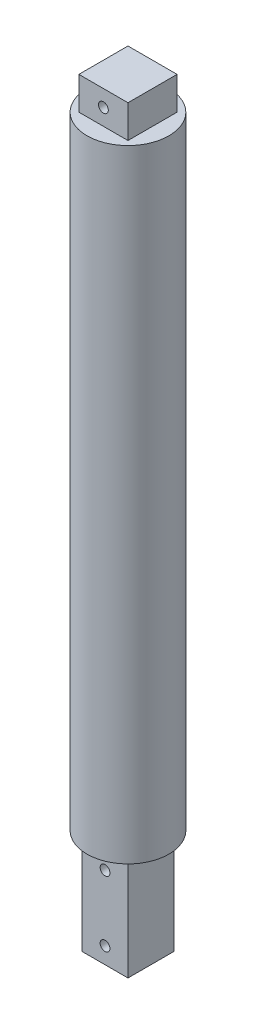
SolidWorks part; units mm, degrees
material "1060 Alloy"
ref_plane "Front Plane" through (0, 0, 0) normal (0, 0, 1) x (1, 0, 0)
ref_plane "Top Plane" through (0, 0, 0) normal (0, 1, 0) x (1, 0, 0)
ref_plane "Right Plane" through (0, 0, 0) normal (1, 0, 0) x (0, 0, -1)
sketch "Sketch1" plane through (0, 0, 0) normal (0, 0, 1) x (1, 0, 0)
  line L0 (0, 0) -> (0, -14105.0389) construction
  line L1 (-7, 32) -> (7, 32)
  line L2 (-7, 32) -> (-7, 0)
  line L3 (-7, 0) -> (7, 0)
  line L4 (7, 32) -> (7, 0)
  circle A0 centre (0, 5) radius 1.5
  circle A1 centre (0, 25) radius 1.5
  point P5 (0, 0)
  dimension "D4" = 3
  dimension "D5" = 3
  dimension "D1" = 14
  dimension "D2" = 32
  dimension "D3" = 20
  dimension "D6" = 5
extrude "Boss-Extrude1" add sketch "Sketch1" along normal mid plane 14
sketch "Sketch3" plane through (0, 32, 0) normal (0, 1, 0) x (1, 0, 0)
  circle A0 centre (0, 0) radius 12.5
  dimension "D1" = 25
extrude "Boss-Extrude2" add sketch "Sketch3" along normal blind 200
sketch "Sketch4" plane through (0, 232, 0) normal (0, 1, 0) x (1, 0, 0)
  line L1 (-7.5, 7.5) -> (7.5, 7.5)
  line L2 (-7.5, 7.5) -> (-7.5, -7.5)
  line L3 (-7.5, -7.5) -> (7.5, -7.5)
  line L4 (7.5, 7.5) -> (7.5, -7.5)
  line L5 (-7.5, 7.5) -> (7.5, -7.5) construction
  line L6 (-7.5, -7.5) -> (7.5, 7.5) construction
  point P0 (0, 0)
  dimension "D1" = 15
  dimension "D2" = 15
extrude "Cut-Extrude1" cut sketch "Sketch4" against normal blind 10 flip side to cut
sketch "Sketch5" plane through (0, 0, 7.5) normal (0, 0, 1) x (1, 0, 0)
  line L0 (-7.5, 227) -> (7.5, 227) construction
  line L1 (-7.5, 222) -> (-7.5, 232) construction
  line L2 (7.5, 222) -> (7.5, 232) construction
  line L3 (0, 232) -> (0, 222) construction
  line L4 (-7.5, 232) -> (7.5, 232) construction
  line L5 (12.5, 222) -> (-12.5, 222) construction
  circle A0 centre (0, 227) radius 1.5
  dimension "D1" = 3
extrude "Cut-Extrude2" cut sketch "Sketch5" against normal through all
